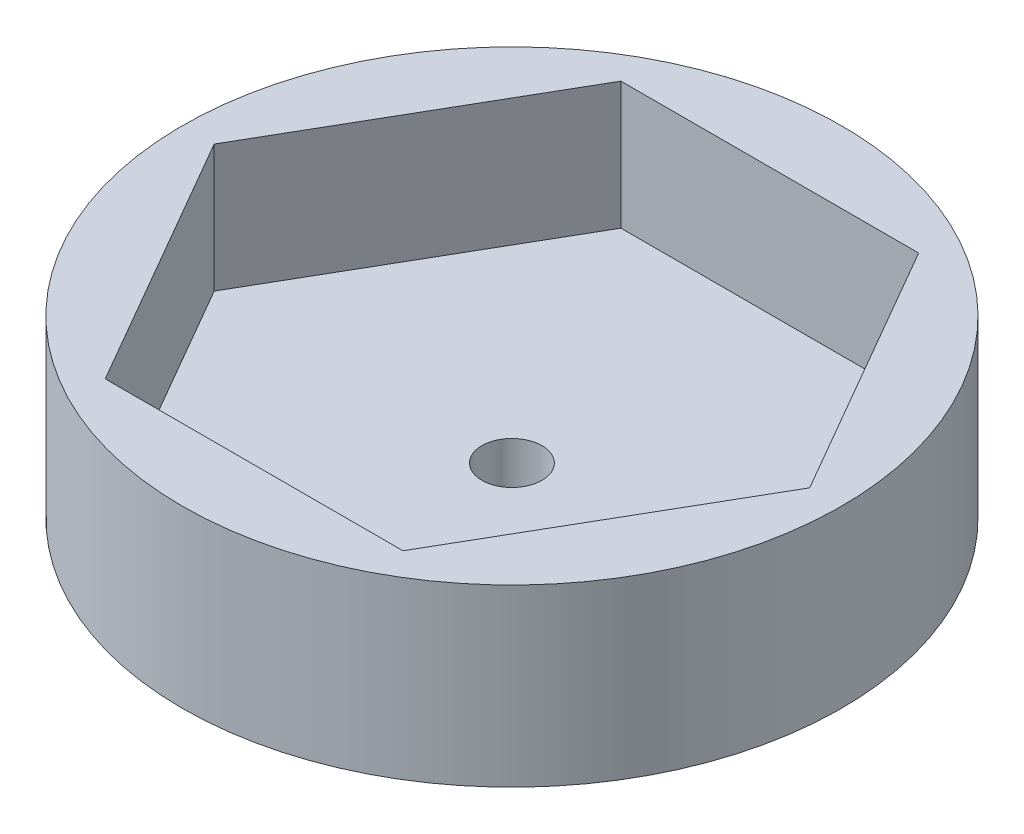
SolidWorks part; units mm, degrees
material "ABS"
ref_plane "Front Plane" through (0, 0, 0) normal (0, 0, 1) x (1, 0, 0)
ref_plane "Top Plane" through (0, 0, 0) normal (0, 1, 0) x (1, 0, 0)
ref_plane "Right Plane" through (0, 0, 0) normal (1, 0, 0) x (0, 0, -1)
sketch "Sketch1" plane through (0, 0, 0) normal (0, 1, 0) x (1, 0, 0)
  circle A0 centre (0, 0) radius 93.5205
  circle A1 centre (0, 0) radius 9.4375
  dimension "D1" = 18.875
  dimension "D2" = 187.041
extrude "Boss-Extrude1" add sketch "Sketch1" along normal blind 15
sketch "Sketch2" plane through (0, 15, 0) normal (0, 1, 0) x (1, 0, 0)
  circle A1 centre (0, 0) radius 93.5205 construction
  circle A2 centre (0, 0) radius 93.5205
  circle A4 centre (0, 0) radius 103.5205
  dimension "D1" = 10
extrude "Boss-Extrude2" add sketch "Sketch2" along normal blind 40 and the other way up to surface (15 mm away) other way up to face at (0, 0, 93.5205)
sketch "Sketch3" plane through (0, 15, 0) normal (0, 1, 0) x (1, 0, 0)
  line L1 (93.5205, 0) -> (46.7603, 80.9911)
  line L2 (46.7603, 80.9911) -> (-46.7602, 80.9911)
  line L3 (-46.7602, 80.9911) -> (-93.5205, 0)
  line L4 (-93.5205, 0) -> (-46.7603, -80.9911)
  line L5 (-46.7603, -80.9911) -> (46.7602, -80.9911)
  line L6 (46.7602, -80.9911) -> (93.5205, 0)
  circle A0 centre (0, 0) radius 93.5205 construction
  circle A1 centre (0, 0) radius 93.5205 construction
  point P1 (65.7621, -18.8891)
  point P12 (0, 0)
  circle M7 centre (0, 0) radius 93.5205
extrude "Boss-Extrude3" add sketch "Sketch3" along normal up to surface (40 mm away) contours L4 M7 | L3 M7 | L2 M7 | L1 M7 | L6 M7 | L5 M7 region at (74.5066, 15, 43.0164) region at (74.5066, 15, -43.0164) region at (0, 15, -86.0328) region at (0, 15, 86.0328) region at (-74.5066, 15, -43.0164) region at (-74.5066, 15, 43.0164) up to face at (0, 55, 103.5205)
equation "\"Rope\"= 5in / 8"
equation "\"D1@Sketch1\"=\"Rope\"+1in\\8"
